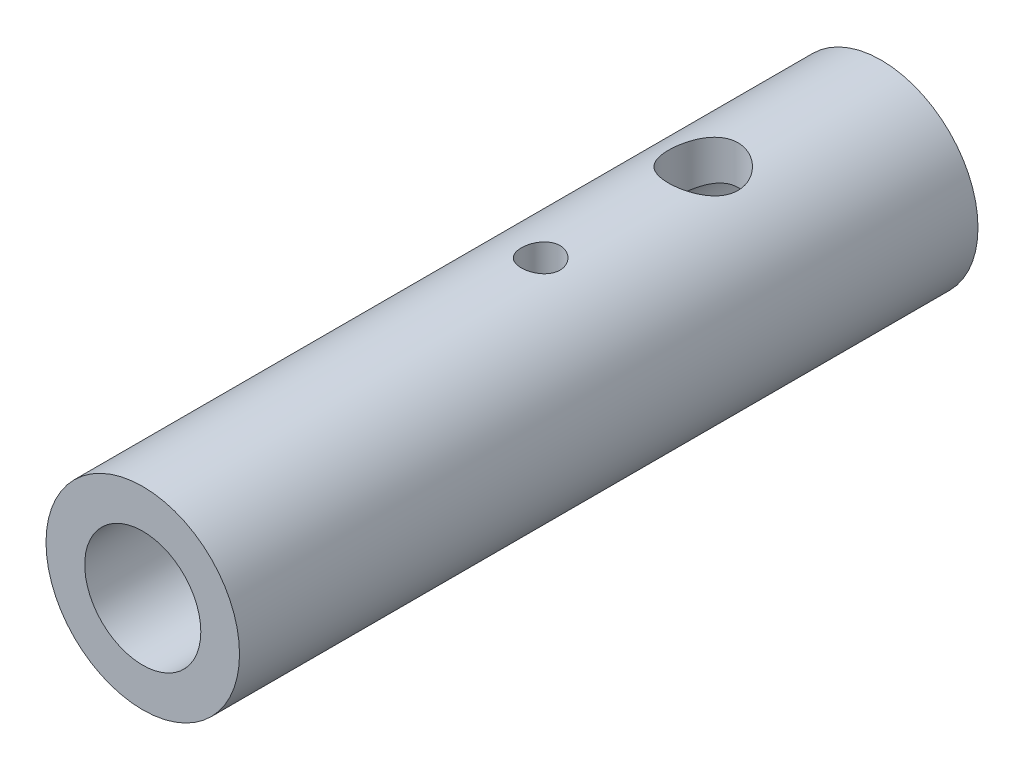
SolidWorks part; units mm, degrees
ref_plane "Front Plane" through (0, 0, 0) normal (0, 0, 1) x (1, 0, 0)
ref_plane "Top Plane" through (0, 0, 0) normal (0, 1, 0) x (1, 0, 0)
ref_plane "Right Plane" through (0, 0, 0) normal (1, 0, 0) x (0, 0, -1)
sketch "Sketch1" plane through (0, 0, 0) normal (0, 0, 1) x (1, 0, 0)
  circle A0 centre (0, 0) radius 7.9375
  circle A1 centre (0, 0) radius 4.7625
  dimension "D1" = 15.875
  dimension "D2" = 9.525
extrude "Boss-Extrude1" add sketch "Sketch1" along normal blind 60.579
sketch "Sketch2" plane through (0, 0, 0) normal (0, 1, 0) x (1, 0, 0)
  line L0 (7.9375, 0) -> (-7.9375, 0) construction
  circle A0 centre (0, -14.605) radius 2.8575
  dimension "D1" = 5.715
  dimension "D2" = 14.605
extrude "Cut-Extrude1" cut sketch "Sketch2" against normal blind 60.579 and the other way blind 60.579
sketch "Sketch3" plane through (0, 0, 0) normal (0, 1, 0) x (1, 0, 0)
  line L0 (7.9375, 0) -> (-7.9375, 0) construction
  circle A0 centre (0, -27.94) radius 1.5875
  dimension "D1" = 3.175
  dimension "D2" = 27.94
extrude "Cut-Extrude2" cut sketch "Sketch3" against normal blind 60.579 and the other way blind 60.579
